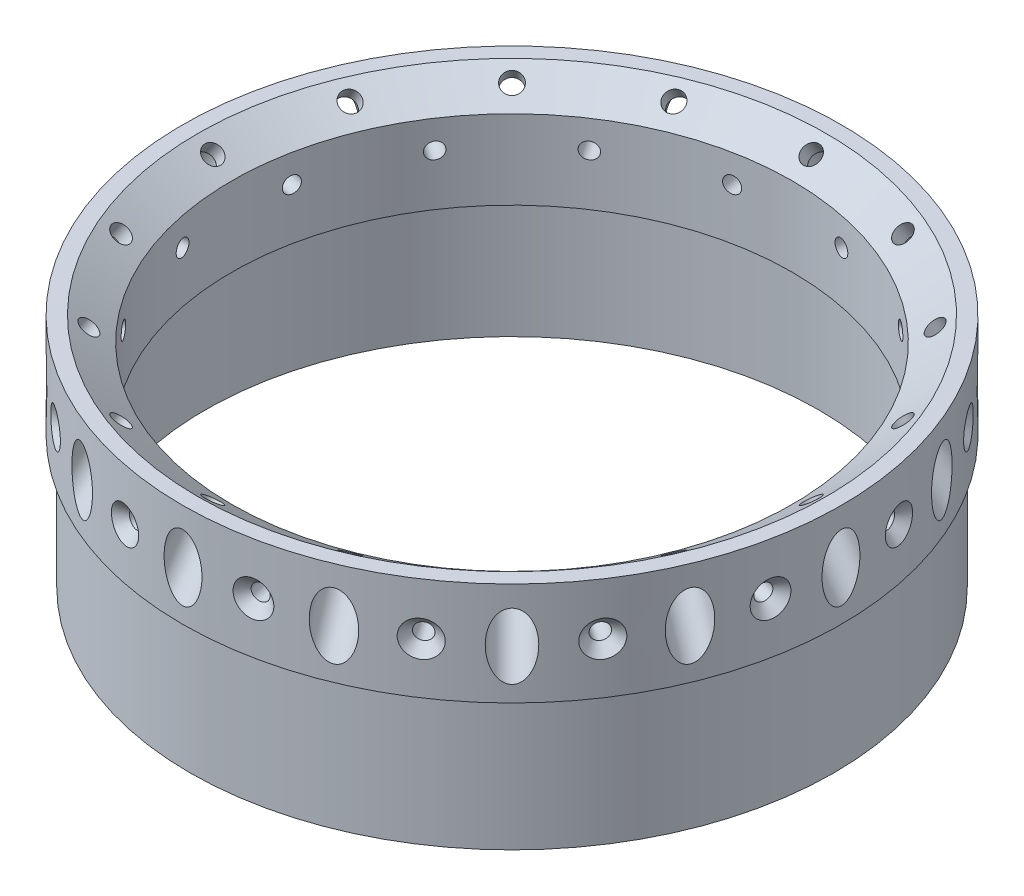
SolidWorks part; units mm, degrees
material "6061 Alloy"
ref_plane "Front Plane" through (0, 0, 0) normal (0, 0, 1) x (1, 0, 0)
ref_plane "Top Plane" through (0, 0, 0) normal (0, 1, 0) x (1, 0, 0)
ref_plane "Right Plane" through (0, 0, 0) normal (1, 0, 0) x (0, 0, -1)
sketch "Main sketch" plane through (0, 0, 0) normal (0, 0, 1) x (1, 0, 0)
  line L0 (0, 0) -> (-87, 0) construction
  line L8 (-85, -35) -> (-81, -35)
  line L23 (-87, 0) -> (-87, 27.1992)
  line L24 (-83, 27.1992) -> (-74, 20.8973)
  line L25 (-74, 20.8973) -> (-74, 0)
  line L26 (-74, 0) -> (-81, 0)
  line L27 (-81, 0) -> (-81, -35)
  line L28 (-87, 0) -> (-85, 0)
  line L29 (-85, 0) -> (-85, -35)
  line L30 (0, 0) -> (0, -35.5238) construction
  line L31 (-87, 27.1992) -> (-83, 27.1992)
  line L32 (-74, 20.8973) -> (-87, 20.8973) construction
  point P4 (-87, 30)
  dimension "D1" = 87
  dimension "D2" = 2
  dimension "D3" = 4
  dimension "D4" = 55
  dimension "D5" = 30
  dimension "D6" = 13
  dimension "D7" = 35
  dimension "D8" = 4
  dimension "D9" = 90
revolve "Main revolve" add sketch "Main sketch" angle 360 about L30
sketch "Hole position" plane through (0, 0, 0) normal (0, 0, 1) x (1, 0, 0)
  line L0 (-79, 24.3983) -> (-83, 18.6857) construction
  line L1 (-83, 27.1992) -> (-74, 20.8973) construction
  line L2 (0, 30) -> (0, -2.3509) construction
  line L4 (-83, 27.1992) -> (-83, -10.9444) construction
  line L6 (87, 30) -> (-87, 30) construction
  line L7 (-83, 18.6857) -> (-67.2656, 7.6684) construction
  point P7 (-79, 24.3983)
  dimension "D1" = 4
ref_plane "Hole plane" through (-18.5267, -26.4589, 0) normal (-0.5736, -0.8192, 0) x (0.8192, -0.5736, 0)
sketch "Sketch14" plane through (-18.5267, -26.4589, 0) normal (-0.5736, -0.8192, 0) x (0.8192, -0.5736, 0)
  circle A1 centre (-78.7073, 0) radius 5
  dimension "D1" = 5
extrude "Hole extrude 1" cut sketch "Sketch14" against normal blind 3 and the other way through all
hole_wizard "screw extrude" positions "3DSketch13" profile "Sketch15" hole size "Ø5.0" standard "DIN" end condition up to next
sketch3d "3DSketch13"
  line L0 (-79, 24.3983, 0) -> (-83, 18.6857, 0) construction
  point P0 (-81.2793, 21.1432, 0)
sketch "Sketch15" plane through (-81.2793, 21.1432, 0) normal (0, 0, 1) x (0.8192, -0.5736, 0)
  line L0 (0, 0) -> (0, 3.9738)
  line L1 (0, 3.9738) -> (2.5, 3.9738)
  line L2 (2.5, 3.9738) -> (2.5, 0)
  line L5 (2.5, 0) -> (0, 0)
  line L11 (0, -6.35) -> (0, 107.95) construction
  dimension "Thru Hole Dia." = 5
  dimension "Thru Hole Depth" = 3.9738
pattern_circular "Screw holes pattern" count 16 over 360 about axis through (0, 0, 0) along (0, 1, 0) of "Hole extrude 1", "screw extrude" reverse direction yes
ref_plane "Płaszczyzna1" through (16.9729, 0, 85.3283) normal (0.1951, 0, 0.9808) x (0, 1, 0)
sketch "Szkic2" plane through (16.9729, 0, 85.3283) normal (0.1951, 0, 0.9808) x (0, 1, 0)
  line L0 (27.1992, -87) -> (27.1992, 87) construction
  circle A0 centre (13.6992, 0) radius 1.65
  dimension "D1" = 13.5
hole_wizard "Pogłębienie stożkowe pod M4 wkręt do części metalowych z łbem soczewkowym1" positions "Szkic12" profile "Szkic13" countersink size "M4" standard "Ansi Metric" end condition up to next
sketch "Szkic12" plane through (16.9729, 0, 85.3283) normal (0.1951, 0, 0.9808) x (0, 1, 0)
  point P0 (13.5, 0)
sketch "Szkic13" plane through (16.9729, 13.5, 85.3283) normal (0, 1, 0) x (0.9808, 0, -0.1951)
  line L0 (0, 0) -> (0, 13)
  line L1 (0, 13) -> (2.15, 13)
  line L2 (2.15, 13) -> (2.15, 2.55)
  line L3 (2.15, 2.55) -> (4.7, 0)
  line L5 (4.7, 0) -> (0, 0)
  line L6 (-2.15, 2.55) -> (-4.7, 0) construction
  line L11 (0, -6.35) -> (0, 107.95) construction
  dimension "Średnica otworu na wylot" = 4.3
  dimension "Głębokość otworu na wylot" = 13
  dimension "Średnica zewnętrznego pogłębienia stożkowego" = 9.4
  dimension "Kąt zewnętrznego pogłębienia stożkowego" = 90
pattern_circular "Szyk kołowy1" count 16 over 360 about axis through (0, 0, 0) along (0, 1, 0) of "Pogłębienie stożkowe pod M4 wkręt do części metalowych z łbem soczewkowym1"
